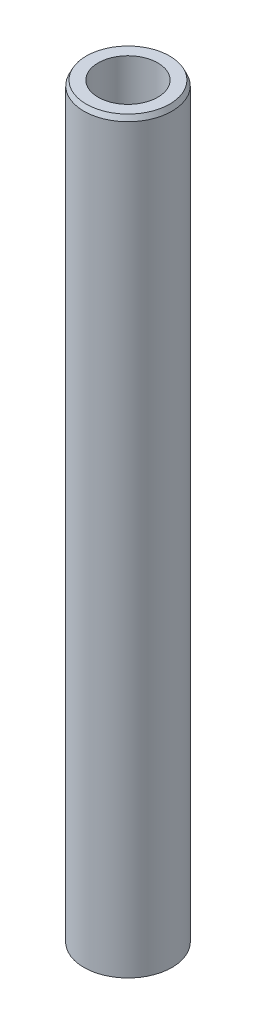
SolidWorks part; units mm, degrees
ref_plane "Front Plane" through (0, 0, 0) normal (0, 0, 1) x (1, 0, 0)
ref_plane "Top Plane" through (0, 0, 0) normal (0, 1, 0) x (1, 0, 0)
ref_plane "Right Plane" through (0, 0, 0) normal (1, 0, 0) x (0, 0, -1)
sketch "Sketch1" plane through (0, 0, 0) normal (0, 1, 0) x (1, 0, 0)
  circle A0 centre (0, 0) radius 32.5
  dimension "SHAFT_OD" = 65
extrude "Boss-Extrude1" add sketch "Sketch1" along normal blind 552.3944
sketch "Sketch2" plane through (0, 0, 0) normal (0, 1, 0) x (1, 0, 0)
  circle A0 centre (0, 0) radius 21.9899
  dimension "BORE_D" = 43.9798
extrude "Cut-Extrude1" cut sketch "Sketch2" along normal through all
chamfer "Chamfer1" distance 3.6442 angle 25.468 2 edges at (0, 552.3944, 32.5) (0, 0, 32.5) first distance on face at (0, 552.3944, 32.5) first distance on face at (0, 0, 21.9899)
